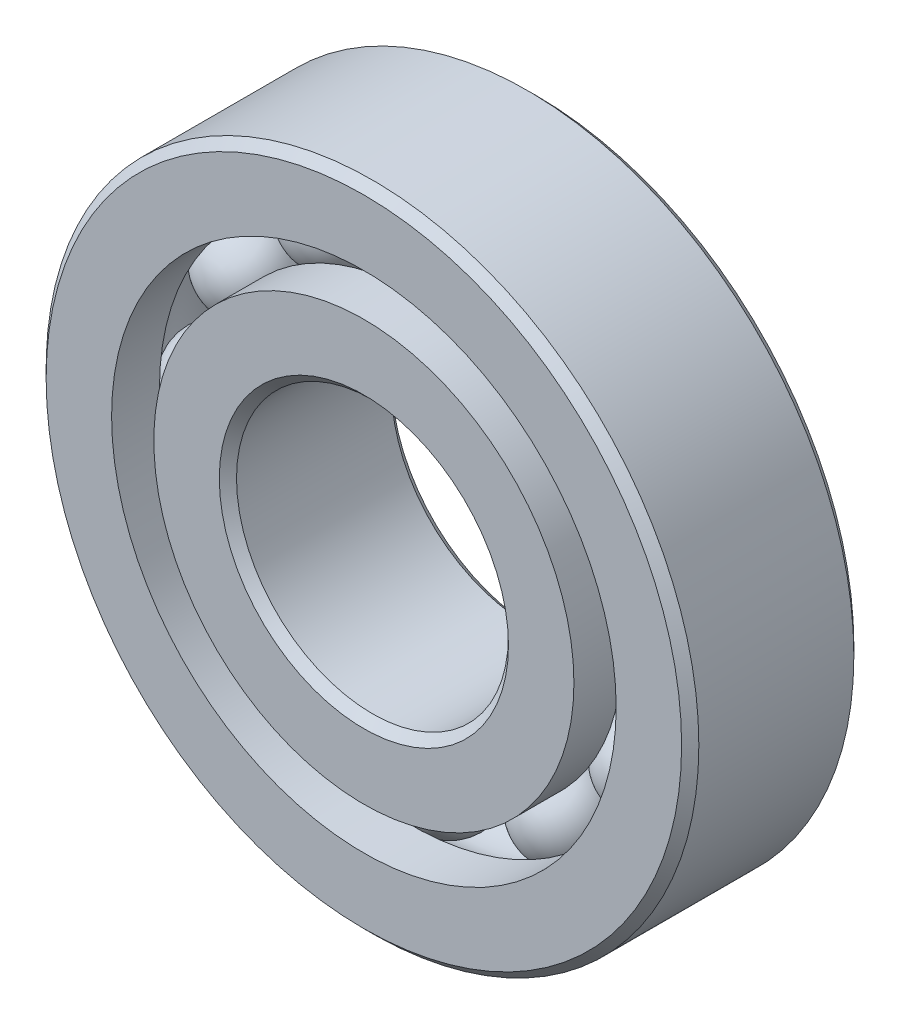
SolidWorks part; units mm, degrees
ref_plane "Front Plane" through (0, 0, 0) normal (0, 0, 1) x (1, 0, 0)
ref_plane "Top Plane" through (0, 0, 0) normal (0, 1, 0) x (1, 0, 0)
ref_plane "Right Plane" through (0, 0, 0) normal (1, 0, 0) x (0, 0, -1)
sketch "Sketch1" plane through (0, 0, 0) normal (1, 0, 0) x (0, 0, -1)
  line L0 (-9.5, 0) -> (9.5, 0) construction
  line L1 (0, 36) -> (0, -36) construction
  line L2 (8.55, 36) -> (-8.55, 36)
  line L3 (-8.55, 36) -> (-9.5, 35.05)
  line L4 (-9.5, 35.05) -> (-9.5, 27.8297)
  line L5 (-9.5, 27.8297) -> (-4.2222, 27.8297)
  line L6 (9.5, 27.8297) -> (4.2222, 27.8297)
  line L7 (9.5, 35.05) -> (9.5, 27.8297)
  line L8 (8.55, 36) -> (9.5, 35.05)
  line L9 (0, 36) -> (0, 25.5) construction
  line L10 (0, 25.5) -> (0, 15) construction
  arc A0 (-4.2222, 27.8297) -> (4.2222, 27.8297) centre (0, 25.5) cw
  point P14 (0, 15)
  dimension "Width" = 19
  dimension "OD" = 72
  dimension "D1" = 45
  dimension "D2" = 0.95
  dimension "Shaft Dia" = 30
  dimension "D3" = 8.4444
  dimension "D4" = 2.3297
revolve "Revolve1" add sketch "Sketch1" angle 360 about L0
sketch "Sketch3" plane through (0, 0, 0) normal (1, 0, 0) x (0, 0, -1)
  line L0 (-9.5, 23.1703) -> (-4.2222, 23.1703)
  line L1 (0, 36) -> (0, -36) construction
  line L2 (-9.5, 35.05) -> (-9.5, 27.8297) construction
  line L3 (-9.5, 23.1703) -> (-9.5, 15.95)
  line L4 (-8.55, 36) -> (-9.5, 35.05) construction
  line L5 (-9.5, 15.95) -> (-8.55, 15)
  line L6 (-8.55, 15) -> (8.55, 15)
  line L7 (8.55, 36) -> (8.55, -36) construction
  line L8 (8.55, 15) -> (9.5, 15.95)
  line L9 (9.5, -35.05) -> (9.5, 35.05) construction
  line L10 (9.5, 15.95) -> (9.5, 23.1703)
  line L11 (9.5, 23.1703) -> (4.2222, 23.1703)
  line L13 (8.55, 36) -> (9.5, 35.05) construction
  arc A0 (4.2222, 27.8297) -> (-4.2222, 27.8297) centre (0, 25.5) ccw construction
  arc A1 (4.2222, 23.1703) -> (-4.2222, 23.1703) centre (0, 25.5) cw
revolve "Revolve3" add sketch "Sketch3" angle 360 about L0
sketch "Sketch4" plane through (0, 0, 0) normal (1, 0, 0) x (0, 0, -1)
  line L0 (-4.8223, 25.5) -> (4.8223, 25.5)
  arc A2 (-4.8223, 25.5) -> (4.8223, 25.5) centre (0, 25.5) cw
  arc A3 (4.2222, 27.8297) -> (-4.2222, 27.8297) centre (0, 25.5) ccw construction
revolve "Revolve4" add sketch "Sketch4" angle 360 about L0
ref_axis "Axis1" through (0, 0, -9.5) along (0, 0, 1)
pattern_circular "CirPattern1" count 12 every 30 about axis through (0, 0, -9.5) along (0, 0, 1) of bodies 104
sketch "Sketch5" plane through (0, 0, 0) normal (1, 0, 0) x (0, 0, -1)
  line L0 (-9.5, 27.8297) -> (-4.2222, 27.8297) construction
  line L1 (-9.025, 27.8297) -> (-4.8223, 27.8297)
  line L2 (-9.025, 27.8297) -> (-9.025, 23.1703)
  line L3 (-9.025, 23.1703) -> (-4.8223, 23.1703)
  line L4 (-4.8223, 27.8297) -> (-4.8223, 23.1703)
  line L5 (-9.5, 23.1703) -> (-4.2222, 23.1703) construction
  line L6 (9.5, 27.8297) -> (4.2222, 27.8297) construction
  line L7 (9.025, 27.8297) -> (4.8223, 27.8297)
  line L8 (9.025, 27.8297) -> (9.025, 23.1703)
  line L9 (9.025, 23.1703) -> (4.8223, 23.1703)
  line L10 (4.8223, 27.8297) -> (4.8223, 23.1703)
  line L11 (9.5, 23.1703) -> (4.2222, 23.1703) construction
  line L12 (-8.55, 36) -> (-9.5, 35.05) construction
  point P18 (-9.025, 35.525)
equation "\"D2@Sketch1\" = \"Width@Sketch1\"*.05"
equation "\"D3@Sketch1\" = \"Width@Sketch1\"/2.25"
equation "\"D4@Sketch1\" = (((\"OD@Sketch1\"-\"Width@Sketch1\")/2)/3.25)/3.5"
equation "\"D2@CirPattern1\" = 360/\"Balls@CirPattern1\""
